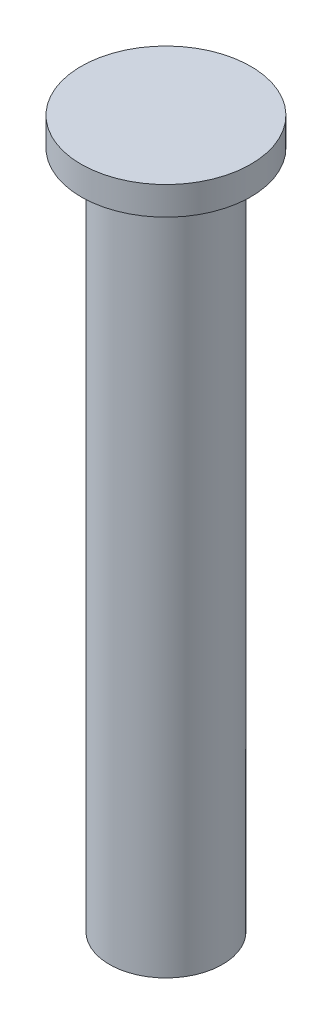
SolidWorks part; units mm, degrees
ref_plane "Спереди" through (0, 0, 0) normal (0, 0, 1) x (1, 0, 0)
ref_plane "Сверху" through (0, 0, 0) normal (0, 1, 0) x (1, 0, 0)
ref_plane "Справа" through (0, 0, 0) normal (1, 0, 0) x (0, 0, -1)
sketch "Эскиз1" plane through (0, 0, 0) normal (0, 1, 0) x (1, 0, 0)
  circle A0 centre (0, 0) radius 10
extrude "Бобышка-Вытянуть1" add sketch "Эскиз1" along normal blind 120
sketch "Эскиз2" plane through (0, 120, 0) normal (0, 1, 0) x (1, 0, 0)
  circle A0 centre (0, 0) radius 15
extrude "Бобышка-Вытянуть2" add sketch "Эскиз2" along normal blind 5
